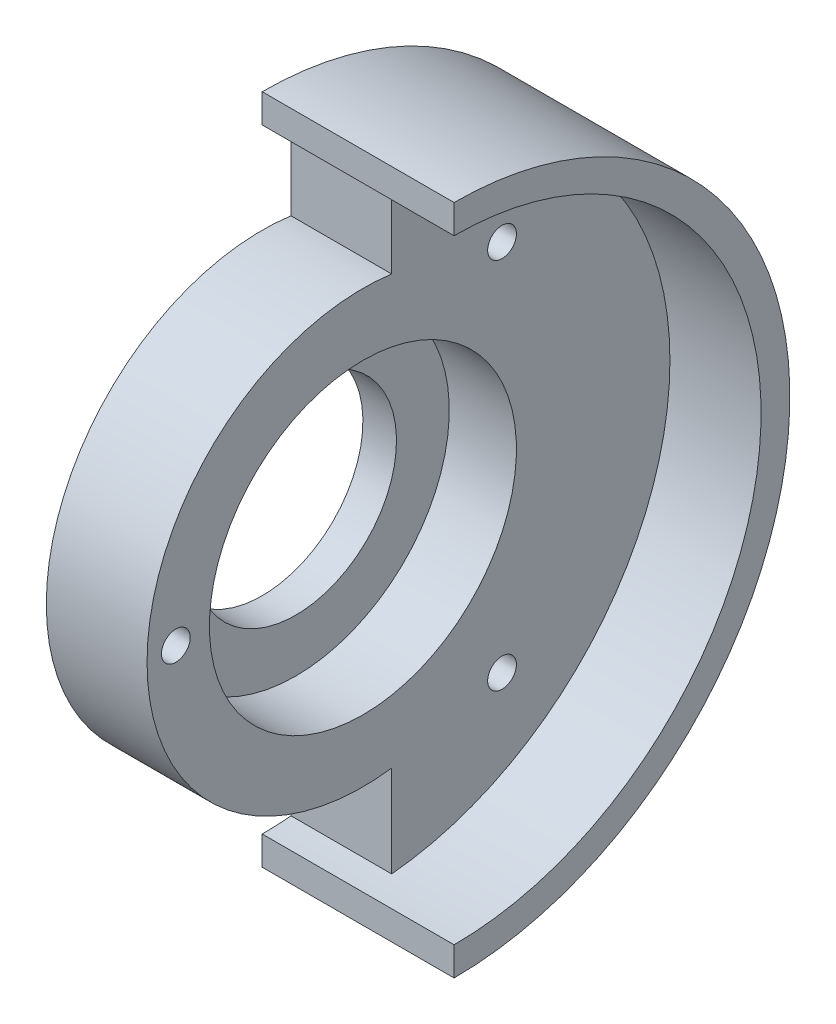
SolidWorks part; units mm, degrees
ref_plane "Front Plane" through (0, 0, 0) normal (0, 0, 1) x (1, 0, 0)
ref_plane "Top Plane" through (0, 0, 0) normal (0, 1, 0) x (1, 0, 0)
ref_plane "Right Plane" through (0, 0, 0) normal (1, 0, 0) x (0, 0, -1)
sketch "Sketch1" plane through (0, 0, 0) normal (0, 0, 1) x (1, 0, 0)
  line L0 (20, 35) -> (20, 32)
  line L1 (20, 32) -> (10.5, 32)
  line L2 (10.5, 32) -> (10.5, 16)
  line L3 (10.5, 16) -> (3.5, 16)
  line L4 (3.5, 16) -> (3.5, 10.5)
  line L5 (3.5, 10.5) -> (0, 10.5)
  line L6 (0, 10.5) -> (0, 35)
  line L7 (0, 35) -> (20, 35)
  line L8 (20, 0) -> (0, 0) construction
  dimension "D1" = 20
  dimension "D2" = 7
  dimension "D3" = 9.5
  dimension "D4" = 10.5
  dimension "D5" = 16
  dimension "D6" = 32
  dimension "D7" = 35
revolve "Revolve1" add sketch "Sketch1" angle 360 about L8
sketch "Sketch2" plane through (10.5, 0, 0) normal (1, 0, 0) x (0, 0, -1)
  line L0 (3, 22.2991) -> (3, 31.8591)
  line L1 (3, -22.2991) -> (3, -31.8591)
  line L2 (0, 35) -> (0, 32)
  line L3 (0, -32) -> (0, -35)
  arc A0 (3, 31.8591) -> (0, 32) centre (0, 0) ccw
  arc A1 (3, 22.2991) -> (3, -22.2991) centre (0, 0) ccw
  circle A2 centre (-19.5, 0) radius 1.5
  circle A3 centre (0, 0) radius 32 construction
  arc A4 (3, 22.2991) -> (3, -22.2991) centre (0, 0) ccw construction
  circle A5 centre (14.5, -19.4374) radius 1.5
  circle A6 centre (14.5, 19.4374) radius 1.5
  circle A7 centre (14.5, 19.4374) radius 1.5 construction
  circle A8 centre (-19.5, 0) radius 1.5 construction
  circle A9 centre (14.5, -19.4374) radius 1.5 construction
  arc A10 (0, 35) -> (0, -35) centre (0, 0) ccw
  circle A11 centre (0, 0) radius 35 construction
  arc A12 (0, -32) -> (3, -31.8591) centre (0, 0) ccw
extrude "Cut-Extrude1" cut sketch "Sketch2" against normal through all both and the other way through all
sketch "Sketch3" plane through (0, 0, 0) normal (-1, 0, 0) x (0, 0, 1)
  circle A0 centre (-14.5, 19.4374) radius 2.75
  circle A1 centre (19.5, 0) radius 2.75
  circle A2 centre (-14.5, -19.4374) radius 2.75
  dimension "D1" = 5.5
extrude "Cut-Extrude2" cut sketch "Sketch3" against normal blind 5
